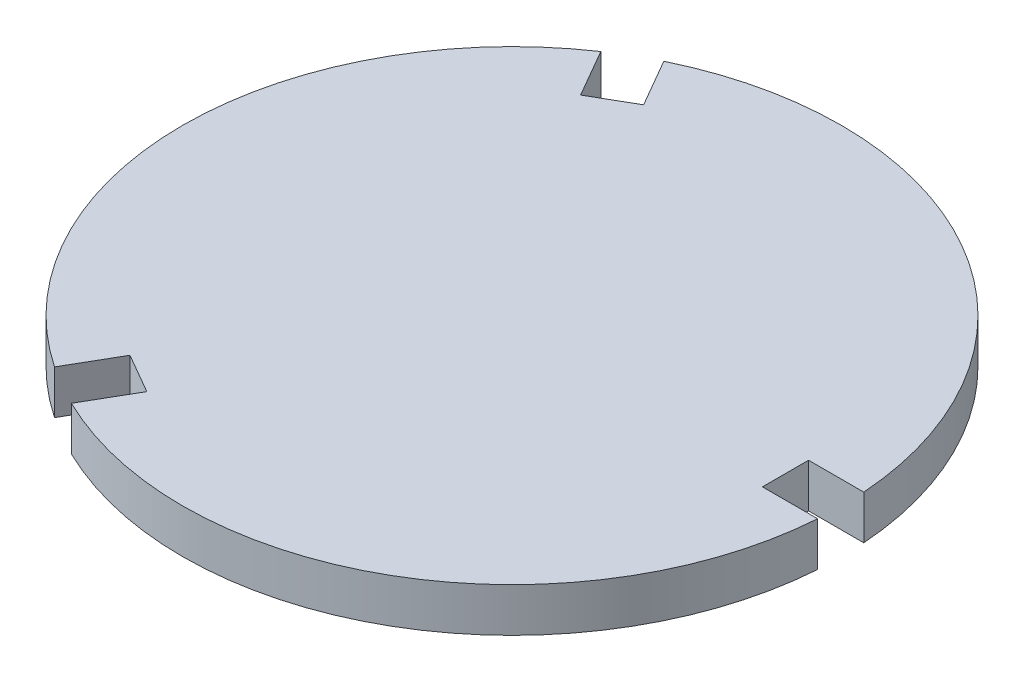
SolidWorks part; units mm, degrees
ref_plane "Alzado" through (0, 0, 0) normal (0, 0, 1) x (1, 0, 0)
ref_plane "Planta" through (0, 0, 0) normal (0, 1, 0) x (1, 0, 0)
ref_plane "Vista lateral" through (0, 0, 0) normal (1, 0, 0) x (0, 0, -1)
sketch "Croquis1" plane through (0, 0, 0) normal (0, 1, 0) x (1, 0, 0)
  circle A2 centre (0, 0) radius 30
  dimension "D2" = 60
extrude "Saliente-Extruir1" add sketch "Croquis1" along normal blind 4
sketch "Croquis2" plane through (0, 0, 0) normal (0, 1, 0) x (1, 0, 0)
  line L0 (0, 0) -> (30, 0) construction
  line L2 (35.1, -2.1) -> (24.9, -2.1)
  line L3 (35.1, -2.1) -> (35.1, 2.1)
  line L4 (35.1, 2.1) -> (24.9, 2.1)
  line L5 (24.9, -2.1) -> (24.9, 2.1)
  line L6 (35.1, -2.1) -> (24.9, 2.1) construction
  line L7 (35.1, 2.1) -> (24.9, -2.1) construction
  circle A1 centre (0, 0) radius 30 construction
  dimension "D1" = 4.2
  dimension "D2" = 10.2
  dimension "D3" = 30
extrude "Cortar-Extruir2" cut sketch "Croquis2" along normal up to next
ref_axis "Eje1" through (0, -0.25, 0) along (0, 1, 0)
pattern_circular "MatrizC1" count 3 over 360 about axis through (0, -0.25, 0) along (0, 1, 0) of "Cortar-Extruir2"
equation "\"dface\"= 80"
equation "\"joind\"=10"
equation "\"thickness\"=4"
equation "\"D1@Croquis2\"=\"thickness\"+\"clear\""
equation "\"D2@Croquis2\"=\"joind\"+\"clear\""
equation "\"D1@Saliente-Extruir1\"=\"thickness\""
equation "\"D2@Croquis1\"=\"dface\" - 2 * \"joind\""
equation "\"clear\"=.2"
equation "\"P\"=.3"
